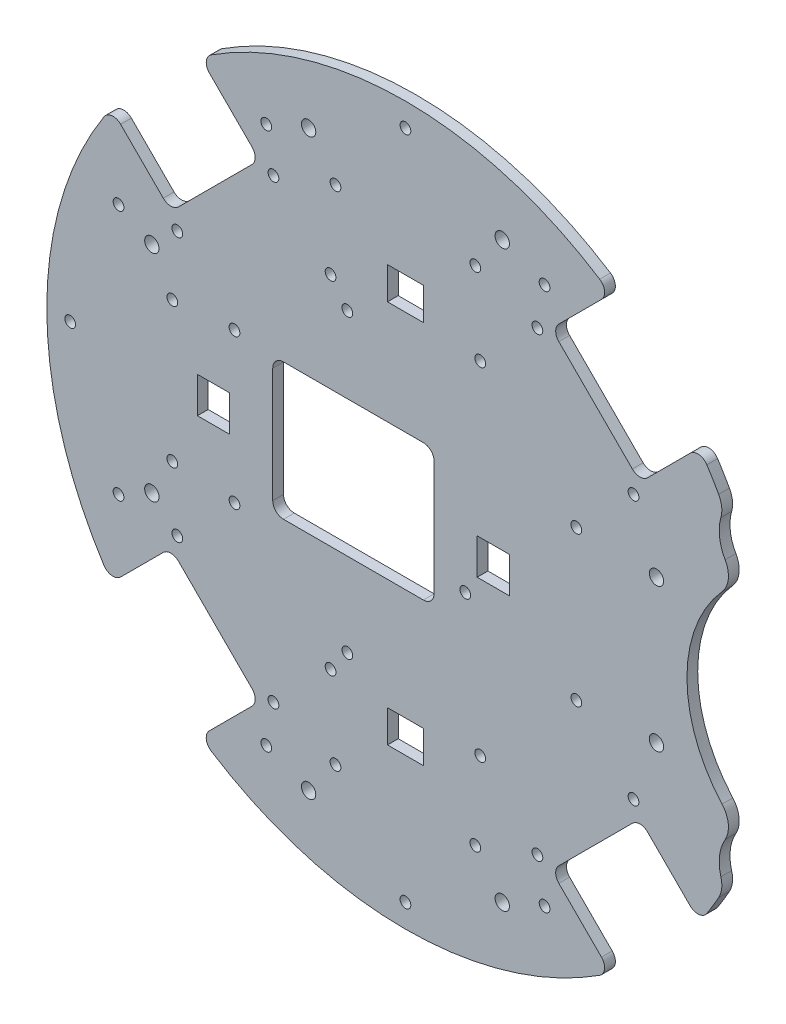
SolidWorks part; units mm, degrees
material "Caoba"
ref_plane "Alzado" through (0, 0, 0) normal (0, 0, 1) x (1, 0, 0)
ref_plane "Planta" through (0, 0, 0) normal (0, 1, 0) x (1, 0, 0)
ref_plane "Vista lateral" through (0, 0, 0) normal (1, 0, 0) x (0, 0, -1)
sketch "Croquis1" plane through (0, 0, 0) normal (0, 0, 1) x (1, 0, 0)
  circle A0 centre (0, 0) radius 100
  dimension "D1" = 200
extrude "Saliente-Extruir1" add sketch "Croquis1" along normal blind 3
sketch "Croquis3" plane through (0, 0, 3) normal (0, 0, 1) x (1, 0, 0)
  line L0 (0, 0) -> (190, 0) construction
  circle A0 centre (190, 0) radius 100
  circle A1 centre (117, 0) radius 38.5
  circle M2 centre (0, 0) radius 100
  dimension "D1" = 200
  dimension "D3" = 77
  dimension "D4" = 117
  dimension "D2" = 190
extrude "Cortar-Extruir1" cut sketch "Croquis3" against normal blind 3 contours L0 A1 A0 M2 | L0 A0 M2 | A1 L0 A0 M2 | A0 L0 M2 region at (95, -11.7494, 3) region at (95, 11.7494, 3) region at (86.3648, -12.4904, 3) region at (86.3648, 12.4904, 3)
sketch "Croquis5" plane through (0, 0, 3) normal (0, 0, 1) x (1, 0, 0)
  line L0 (0, -100) -> (0, 100) construction
  line L1 (-100, 0) -> (78.5, 0) construction
  line L2 (0, 0) -> (-70.7107, -70.7107) construction
  line L3 (-70.7107, -70.7107) -> (70.7107, 70.7107) construction
  line L4 (0, 0) -> (-70.7107, 70.7107) construction
  line L5 (-70.7107, 70.7107) -> (70.7107, -70.7107) construction
  line L6 (-70.7107, -70.7107) -> (-58.3363, -83.085) construction
  line L9 (-58.3363, -83.085) -> (-83.085, -58.3363)
  line L11 (-83.085, -58.3363) -> (-65.4074, -40.6586)
  line L12 (-65.4074, -40.6586) -> (-40.6586, -65.4074)
  line L13 (-40.6586, -65.4074) -> (-58.3363, -83.085)
  line L14 (-70.7107, 70.7107) -> (-83.085, 58.3363) construction
  line L15 (-83.085, 58.3363) -> (-100, 0) construction
  line L17 (-83.085, 58.3363) -> (-58.3363, 83.085)
  line L18 (-58.3363, 83.085) -> (-40.6586, 65.4074)
  line L19 (-40.6586, 65.4074) -> (-65.4074, 40.6586)
  line L20 (-65.4074, 40.6586) -> (-83.085, 58.3363)
  line L22 (70.7107, -70.7107) -> (58.3363, -83.085) construction
  line L23 (58.3363, -83.085) -> (0, -100) construction
  line L24 (58.3363, -83.085) -> (83.085, -58.3363)
  line L25 (83.085, -58.3363) -> (65.4074, -40.6586)
  line L26 (65.4074, -40.6586) -> (40.6586, -65.4074)
  line L27 (40.6586, -65.4074) -> (58.3363, -83.085)
  line L28 (70.7107, 70.7107) -> (58.3363, 83.085) construction
  line L29 (58.3363, 83.085) -> (0, 100) construction
  line L30 (58.3363, 83.085) -> (83.085, 58.3363)
  line L31 (83.085, 58.3363) -> (65.4074, 40.6586)
  line L32 (65.4074, 40.6586) -> (40.6586, 65.4074)
  line L33 (40.6586, 65.4074) -> (58.3363, 83.085)
  circle A0 centre (0, 0) radius 100 construction
  arc A4 (94.9006, 31.5257) -> (94.9006, -31.5257) centre (117, 0) ccw construction
  point P3 (0, 0)
  point P4 (0, 0)
  point P34 (0, 0)
  point P36 (0, 0)
  dimension "D2" = 17.5
  dimension "D3" = 25
  dimension "D4" = 35
  dimension "D5" = 25
  dimension "D6" = 35
  dimension "D8" = 25
  dimension "D9" = 17.5
  dimension "D7" = 35
  dimension "D10" = 90
  dimension "D11" = 17.5
  dimension "D12" = 17.5
  dimension "D13" = 35
  dimension "D14" = 25
  dimension "D15" = 45
  dimension "D16" = 100
extrude "Cortar-Extruir6" cut sketch "Croquis5" against normal blind 10
sketch "Croquis12" plane through (0, 0, 3) normal (0, 0, 1) x (1, 0, 0)
  line L0 (-53.033, -53.033) -> (-39.9421, -50.0116) construction
  line L1 (-40.6586, -65.4074) -> (-65.4074, -40.6586) construction
  line L2 (-39.9421, -50.0116) -> (-36.8049, -63.6043) construction
  line L3 (-36.8049, -63.6043) -> (-63.6043, -36.8049) construction
  line L4 (-63.6043, -36.8049) -> (-47.6661, -20.8667) construction
  line L6 (53.033, -53.033) -> (-53.033, 53.033) construction
  line L7 (65.4074, -40.6586) -> (40.6586, -65.4074) construction
  line L8 (-65.4074, 40.6586) -> (-40.6586, 65.4074) construction
  line L9 (36.8049, 63.6043) -> (20.8667, 47.6661) construction
  line L10 (63.6043, 36.8049) -> (36.8049, 63.6043) construction
  line L11 (50.0116, 39.9421) -> (63.6043, 36.8049) construction
  line L12 (53.033, 53.033) -> (50.0116, 39.9421) construction
  line L14 (53.033, -53.033) -> (50.2046, -50.2046) construction
  line L15 (50.2046, -50.2046) -> (36.8049, -63.6043) construction
  line L16 (36.8049, -63.6043) -> (63.6043, -36.8049) construction
  line L17 (63.6043, -36.8049) -> (47.6661, -20.8667) construction
  line L19 (-53.033, -53.033) -> (53.033, 53.033) construction
  line L20 (-36.8049, 63.6043) -> (-20.8667, 47.6661) construction
  line L21 (-63.6043, 36.8049) -> (-36.8049, 63.6043) construction
  line L22 (-50.2046, 50.2046) -> (-63.6043, 36.8049) construction
  line L23 (-53.033, 53.033) -> (-50.2046, 50.2046) construction
  circle A0 centre (-63.6043, -36.8049) radius 1.5
  circle A1 centre (-36.8049, -63.6043) radius 1.5
  circle A2 centre (-47.6661, -20.8667) radius 1.5
  circle A3 centre (-20.8667, -47.6661) radius 1.5
  circle A5 centre (47.6661, 20.8667) radius 1.5
  circle A6 centre (20.8667, 47.6661) radius 1.5
  circle A7 centre (63.6043, 36.8049) radius 1.5
  circle A8 centre (36.8049, 63.6043) radius 1.5
  circle A10 centre (20.8667, -47.6661) radius 1.5
  circle A11 centre (47.6661, -20.8667) radius 1.5
  circle A12 centre (63.6043, -36.8049) radius 1.5
  circle A13 centre (36.8049, -63.6043) radius 1.5
  circle A15 centre (-63.6043, 36.8049) radius 1.5
  circle A16 centre (-36.8049, 63.6043) radius 1.5
  circle A17 centre (-20.8667, 47.6661) radius 1.5
  circle A18 centre (-47.6661, 20.8667) radius 1.5
  dimension "D2" = 3
  dimension "D3" = 3
  dimension "D4" = 4
  dimension "D5" = 4
  dimension "D6" = 3
  dimension "D7" = 3
  dimension "D8" = 37.9
  dimension "D9" = 22.54
  dimension "D10" = 22.54
  dimension "D11" = 37.9
  dimension "D12" = 18.95
  dimension "D13" = 18.95
  dimension "D14" = 3
  dimension "D15" = 3
  dimension "D16" = 3
  dimension "D17" = 3
  dimension "D18" = 37.9
  dimension "D19" = 22.54
  dimension "D20" = 22.54
  dimension "D21" = 37.9
  dimension "D22" = 4
  dimension "D1" = 13.95
extrude "Cortar-Extruir7" cut sketch "Croquis12" against normal through all
sketch "Croquis9" plane through (0, 0, 3) normal (0, 0, 1) x (1, 0, 0)
  line L0 (0, 0) -> (-100, 0) construction
  line L5 (0, 100) -> (0, -100) construction
  line L6 (20, 5) -> (29, 5)
  line L7 (20, 5) -> (20, -5)
  line L8 (20, -5) -> (29, -5)
  line L9 (29, 5) -> (29, -5)
  line L10 (-5, -49) -> (5, -49)
  line L11 (-49, 5) -> (-58, 5)
  line L12 (-49, 5) -> (-49, -5)
  line L13 (-49, -5) -> (-58, -5)
  line L14 (-58, 5) -> (-58, -5)
  line L15 (-5, 58) -> (5, 58)
  line L16 (-5, 58) -> (-5, 49)
  line L17 (-5, 49) -> (5, 49)
  line L18 (5, 58) -> (5, 49)
  line L19 (5, -58) -> (5, -49)
  line L20 (-5, -58) -> (5, -58)
  line L21 (-5, -58) -> (-5, -49)
  line L22 (0, 0) -> (78.5, 0) construction
  line L24 (-52.061, -4) -> (-52.0837, -4) construction
  arc A2 (94.9006, 31.5257) -> (94.9006, -31.5257) centre (117, 0) ccw construction
  arc A6 (-81.9939, 57.2451) -> (-81.9939, -57.2451) centre (0, 0) ccw construction
  point P2 (0, 0)
  point P3 (0, 0)
  point P13 (0, 0)
  dimension "D7" = 49
  dimension "D8" = 49
  dimension "D9" = 20
  dimension "D10" = 49
  dimension "D28" = 5
  dimension "D37" = 5
  dimension "D62" = 9
  dimension "D32" = 10
  dimension "D50" = 5
  dimension "D17" = 9
  dimension "D18" = 10
  dimension "D33" = 5
  dimension "D47" = 10
  dimension "D48" = 9
  dimension "D66" = 9
  dimension "D67" = 10
extrude "Cortar-Extruir5" cut sketch "Croquis9" against normal blind 10
sketch "Croquis13" plane through (0, 0, 3) normal (0, 0, 1) x (1, 0, 0)
  line L0 (0, 100) -> (0, -100) construction
  line L1 (-100, 0) -> (78.5, 0) construction
  line L2 (-70.7107, 70.7107) -> (70.7107, -70.7107) construction
  line L3 (-70.7093, -70.7093) -> (70.712, 70.712) construction
  line L4 (-70.7107, 70.7107) -> (-70.7093, -70.7093) construction
  line L5 (-70.7093, -70.7093) -> (70.7107, -70.7107) construction
  line L6 (70.7107, -70.7107) -> (70.712, 70.712) construction
  line L7 (70.712, 70.712) -> (-70.7107, 70.7107) construction
  line L9 (-37, 20) -> (8, 20)
  line L10 (-37, 20) -> (-37, -18)
  line L11 (-37, -18) -> (8, -18)
  line L12 (8, 20) -> (8, -18)
  arc A0 (57.2451, 81.9939) -> (-57.2451, 81.9939) centre (0, 0) ccw construction
  arc A1 (-57.2451, -81.9939) -> (57.2451, -81.9939) centre (0, 0) ccw construction
  arc A2 (-81.9939, 57.2451) -> (-81.9939, -57.2451) centre (0, 0) ccw construction
  circle A4 centre (-70.7103, 30) radius 2
  circle A5 centre (-70.7097, -30) radius 2
  circle A9 centre (0, 93.47) radius 1.5
  circle A10 centre (70, -20) radius 2
  circle A11 centre (70, 20) radius 2
  circle A13 centre (0, -93.47) radius 1.5
  circle A14 centre (-93.47, 0) radius 1.5
  arc A15 (94.9006, 31.5257) -> (94.9006, -31.5257) centre (117, 0) ccw construction
  point P13 (0, 0)
  point P37 (-10.75, 0)
  point P47 (0, 0)
  dimension "D9" = 4
  dimension "D10" = 4
  dimension "D11" = 30
  dimension "D12" = 30
  dimension "D13" = 4
  dimension "D14" = 4
  dimension "D15" = 70
  dimension "D16" = 70
  dimension "D17" = 93.47
  dimension "D18" = 3
  dimension "D19" = 93.47
  dimension "D20" = 3
  dimension "D25" = 20
  dimension "D26" = 20
  dimension "D27" = 93.47
  dimension "D28" = 3
  dimension "D1" = 45
  dimension "D2" = 200
  dimension "D3" = 0
  dimension "D4" = 200
  dimension "D5" = 45
  dimension "D6" = 0
  dimension "D7" = 141.42
  dimension "D8" = 141.42
  dimension "D21" = 45
  dimension "D22" = 38
  dimension "D23" = 18
  dimension "D24" = 37
extrude "Cortar-Extruir8" cut sketch "Croquis13" against normal through all
fillet "Redondeo2" radius 3 20 edges at (-81.9939, 57.2451, 1.5) (-65.4074, 40.6586, 1.5) (-40.6586, 65.4074, 1.5) (-57.2451, 81.9939, 1.5) (65.4074, 40.6586, 1.5) (40.6586, 65.4074, 1.5) (57.2451, 81.9939, 1.5) (81.9939, 57.2451, 1.5) (65.4074, -40.6586, 1.5) (40.6586, -65.4074, 1.5) (81.9939, -57.2451, 1.5) (57.2451, -81.9939, 1.5) (-65.4074, -40.6586, 1.5) (-81.9939, -57.2451, 1.5) (-57.2451, -81.9939, 1.5) (-40.6586, -65.4074, 1.5) (8, -18, 1.5) (8, 20, 1.5) (-37, -18, 1.5) (-37, 20, 1.5)
sketch "Croquis14" plane through (0, 0, 3) normal (0, 0, 1) x (1, 0, 0)
  line L0 (42.78, -67.5287) -> (54.6657, -79.4145) construction
  line L1 (0, 0) -> (75.1866, -75.1866) construction
  line L2 (0, 100) -> (0, -100) construction
  line L7 (-100, 0) -> (83.579, 0) construction
  line L8 (0, 0) -> (88.3883, 88.3883) construction
  line L9 (0, 0) -> (-88.3883, -88.3883) construction
  line L10 (0, 0) -> (-74.4604, 74.4604) construction
  circle A0 centre (38.8032, -75) radius 1.5
  circle A1 centre (-80, -35) radius 1.5
  circle A2 centre (-38.7968, -75) radius 1.5
  circle A8 centre (-80, 35) radius 1.5
  circle A9 centre (-38.8032, 75) radius 1.5
  circle A10 centre (38.7968, 75) radius 1.5
  arc A12 (54.1695, 84.0575) -> (-54.1695, 84.0575) centre (0, 0) ccw construction
  arc A13 (-54.1695, -84.0575) -> (54.1695, -84.0575) centre (0, 0) ccw construction
  arc A14 (-84.0575, 54.1695) -> (-84.0575, -54.1695) centre (0, 0) ccw construction
  point P23 (-5.3984, -2.1885)
  point P24 (0, 0)
  dimension "D1" = 3
  dimension "D2" = 8.095
  dimension "D3" = 75
  dimension "D4" = 3
  dimension "D5" = 75
  dimension "D7" = 75
  dimension "D8" = 38.7968
  dimension "D9" = 75
  dimension "D10" = 38.8032
  dimension "D11" = 3
  dimension "D12" = 3
  dimension "D13" = 70
  dimension "D14" = 35
  dimension "D15" = 80
  dimension "D16" = 80
  dimension "D17" = 3
  dimension "D18" = 3
  dimension "D24" = 77.6
  dimension "D6" = 125
  dimension "D19" = 125
  dimension "D20" = 45
  dimension "D21" = 45
  dimension "D22" = 45
  dimension "D23" = 45
extrude "Cortar-Extruir9" cut sketch "Croquis14" against normal through all
sketch "Croquis15" plane through (0, 0, 0) normal (0, 0, -1) x (-1, 0, 0)
  line L0 (0, 100) -> (0, -100) construction
  line L1 (-78.5, 0) -> (100, 0) construction
  circle A0 centre (16.19, 41.3081) radius 1.5
  circle A1 centre (16.19, -41.3181) radius 1.5
  arc A2 (54.1695, 84.0575) -> (-54.1695, 84.0575) centre (0, 0) ccw construction
  arc A3 (-54.1695, -84.0575) -> (54.1695, -84.0575) centre (0, 0) ccw construction
  arc A5 (84.0575, -54.1695) -> (84.0575, 54.1695) centre (0, 0) ccw construction
  circle A6 centre (-16.705, -10.3179) radius 1.5
  arc A7 (-94.9006, -31.5257) -> (-94.9006, 31.5257) centre (-117, 0) ccw construction
  point P14 (0, 0)
  dimension "D1" = 3
  dimension "D2" = 3
  dimension "D3" = 82.6262
  dimension "D4" = 16.19
  dimension "D5" = 41.3182
  dimension "D6" = 41.3081
  dimension "D7" = 3
  dimension "D8" = 51.626
  dimension "D9" = 32.895
extrude "Cortar-Extruir10" cut sketch "Croquis15" against normal blind 10
sketch "Croquis16" plane through (0, 0, 0) normal (0, 0, -1) x (-1, 0, 0)
  line L0 (0, 100) -> (0, -100) construction
  line L1 (-78.5, 0) -> (100, 0) construction
  circle A0 centre (-19.5, 70) radius 1.5
  circle A1 centre (19.5, 70) radius 1.5
  arc A2 (54.1695, 84.0575) -> (-54.1695, 84.0575) centre (0, 0) ccw construction
  arc A3 (-54.1695, -84.0575) -> (54.1695, -84.0575) centre (0, 0) ccw construction
  arc A5 (84.0575, -54.1695) -> (84.0575, 54.1695) centre (0, 0) ccw construction
  circle A6 centre (19.5, -70) radius 1.5
  circle A7 centre (-19.5, -70) radius 1.5
  circle A8 centre (65, 19.5) radius 1.5
  circle A9 centre (65, -19.5) radius 1.5
  circle A10 centre (-27, 80) radius 2
  circle A11 centre (27, 80) radius 2
  circle A12 centre (27, -80) radius 2
  circle A13 centre (-27, -80) radius 2
  arc A14 (-94.9006, -31.5257) -> (-94.9006, 31.5257) centre (-117, 0) ccw construction
  point P14 (0, 0)
  dimension "D1" = 3
  dimension "D2" = 3
  dimension "D3" = 39
  dimension "D4" = 19.5
  dimension "D5" = 70
  dimension "D6" = 19.5
  dimension "D7" = 3
  dimension "D8" = 3
  dimension "D9" = 39
  dimension "D10" = 19.5
  dimension "D11" = 19.5
  dimension "D12" = 65
  dimension "D13" = 4
  dimension "D14" = 27
  dimension "D15" = 80
extrude "Cortar-Extruir11" cut sketch "Croquis16" against normal blind 10
sketch "Croquis17" plane through (0, 0, 0) normal (0, 0, -1) x (-1, 0, 0)
  line L0 (0, 0) -> (-130, 0) construction
  circle A0 centre (-100, 40) radius 12.5
  circle A1 centre (-100, -40) radius 12.5
  dimension "D1" = 25
  dimension "D2" = 100
  dimension "D3" = 40
  dimension "D4" = 130
extrude "Cortar-Extruir12" cut sketch "Croquis17" against normal blind 10
fillet "Redondeo3" radius 7 4 edges at (88.911, -45.7693, 1.5) (92.694, -29.8574, 1.5) (88.911, 45.7693, 1.5) (92.694, 29.8574, 1.5)
